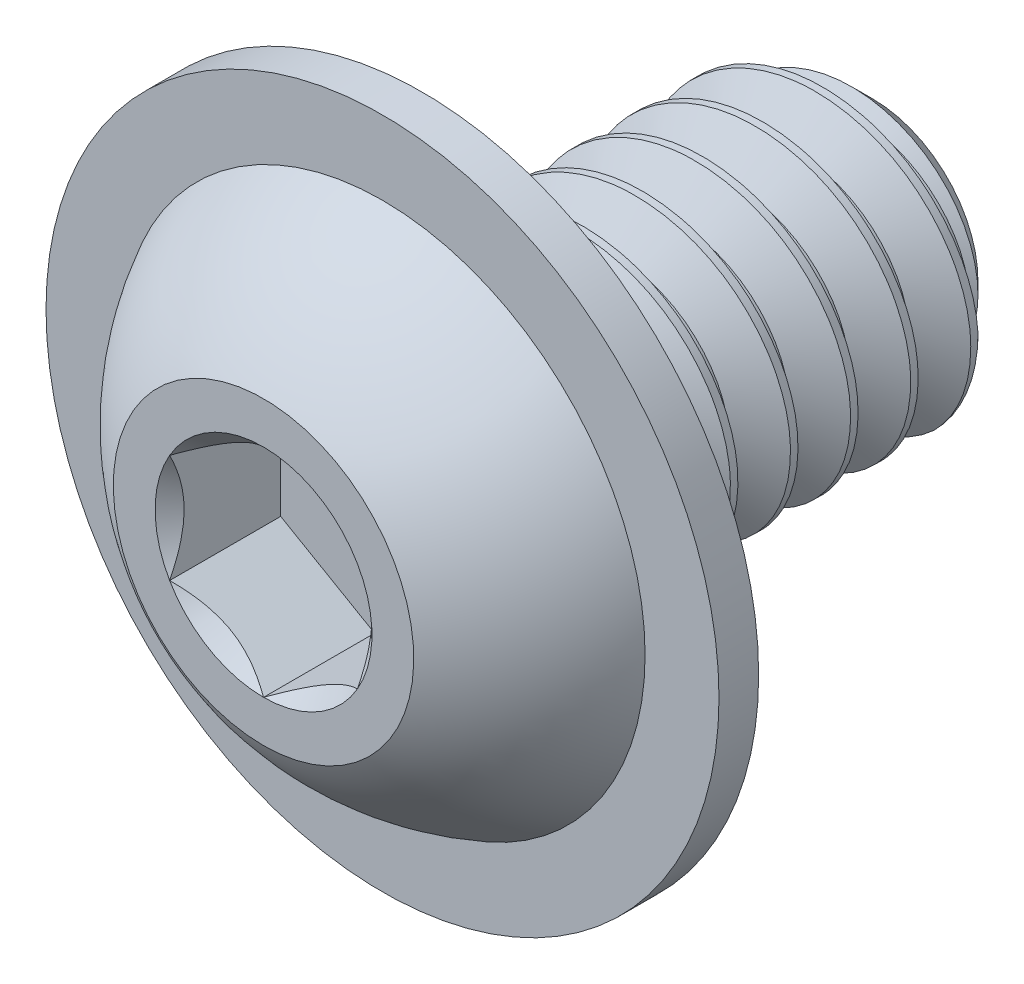
SolidWorks part; units mm, degrees
material "Cast Alloy Steel"
ref_plane "Front" through (0, 0, 0) normal (0, 0, 1) x (1, 0, 0)
ref_plane "Top" through (0, 0, 0) normal (0, 1, 0) x (1, 0, 0)
ref_plane "Right" through (0, 0, 0) normal (1, 0, 0) x (0, 0, -1)
sketch "Sketch1" plane through (0, 0, 0) normal (1, 0, 0) x (0, 0, -1)
  line L2 (3.3528, 3.175) -> (12.8778, 3.175)
  line L3 (12.8778, 3.175) -> (12.8778, 0)
  line L4 (12.8778, 0) -> (3.3528, 0)
  line L6 (2.5146, 5.5499) -> (3.3528, 5.5499) construction
  line L7 (12.8778, 3.175) -> (12.8778, -3.175) construction
  line L8 (0, 0) -> (3.3528, 0) construction
  line L9 (3.3528, 5.5499) -> (3.3528, -5.5499) construction
  line L11 (3.3528, 3.175) -> (3.3528, 0)
  line L13 (0, 1.9844) -> (0, -1.9844) construction
  line L14 (0, 1.9844) -> (0, 3.175) construction
  line L15 (2.5146, 5.5499) -> (2.5146, 7.112) construction
  line L16 (2.5146, 7.112) -> (3.3528, 7.112) construction
  line L17 (3.3528, 7.112) -> (3.3528, 5.5499) construction
  line L18 (3.3528, 7.112) -> (3.3528, -7.112) construction
  arc A3 (0, 3.175) -> (2.5146, 5.5499) centre (5.3774, 0) cw construction
  dimension "D1" = 0.8382
  dimension "Head Ht" = 3.3528
  dimension "Head Dia" = 11.0998
  dimension "Dia" = 6.35
  dimension "Lg" = 9.525
  dimension "Hex" = 3.9688
  dimension "Flange Dia" = 14.224
revolve "Revolve1" add sketch "Sketch1" angle 360 mid plane about L4
sketch "Sketch3" plane through (0, 0, -12.8778) normal (0, 0, -1) x (-1, 0, 0)
  circle A0 centre (0, 0) radius 3.175
curve "Helix/Spiral1" pitch 1.27 height 10.795 radius 3.175 centre (0, 0, -12.8778) axis (0, 0, 1) start towards (0, 1, 0)
sketch "Sketch2" plane through (0, 0, 0) normal (1, 0, 0) x (0, 0, -1)
  line L0 (12.8778, 3.175) -> (13.989, 3.175)
  line L1 (13.989, 3.175) -> (13.5128, 2.3501)
  line L2 (13.5128, 2.3501) -> (13.354, 2.3501)
  line L3 (13.354, 2.3501) -> (12.8778, 3.175)
  line L4 (13.1159, 2.7626) -> (13.7509, 2.7626) construction
  dimension "D1" = 60
  dimension "D2" = 0.1588
  dimension "D3" = 0.635
chamfer "Chamfer1" distance 0.9525 angle 45 1 edges at (0, 3.175, -12.8778)
sweep "Cut-Sweep1" cut profiles "Sketch2" path "Helix/Spiral1"
sketch "Sketch7" plane through (0, 0, 0) normal (1, 0, 0) x (0, 0, -1)
  line L6 (2.5146, 5.5499) -> (3.3528, 5.5499) construction
  line L8 (0, 0) -> (3.3528, 0) construction
  line L11 (3.3528, 5.5499) -> (3.3528, -5.5499) construction
  line L12 (2.5146, 5.5499) -> (3.3528, 5.5499)
  line L13 (0, 0) -> (3.3528, 0)
  line L14 (0, 1.9844) -> (0, -1.9844) construction
  line L15 (3.3528, 5.5499) -> (3.3528, 0)
  line L16 (0, 3.175) -> (0, 0)
  arc A2 (2.5146, 5.5499) -> (0, 3.175) centre (5.3774, 0) ccw construction
  arc A3 (2.5146, 5.5499) -> (0, 3.175) centre (5.3774, 0) ccw
revolve "Revolve2" add sketch "Sketch7" angle 360 mid plane about L13
sketch "Sketch11" plane through (0, 0, -3.3528) normal (0, 0, -1) x (-1, 0, 0)
  circle A0 centre (0, 0) radius 7.112
extrude "Boss-Extrude3" add sketch "Sketch11" against normal up to vertex (0.8382 mm away) up to point (0, 5.5499, -2.5146)
sketch "Sketch5" plane through (0, 0, 0) normal (0, 0, 1) x (1, 0, 0)
  line L1 (1.9844, -1.1457) -> (1.9844, 1.1457)
  line L2 (1.9844, 1.1457) -> (0, 2.2914)
  line L3 (0, 2.2914) -> (-1.9844, 1.1457)
  line L4 (-1.9844, 1.1457) -> (-1.9844, -1.1457)
  line L5 (-1.9844, -1.1457) -> (0, -2.2914)
  line L6 (0, -2.2914) -> (1.9844, -1.1457)
  circle A0 centre (0, 0) radius 1.9844 construction
extrude "Cut-Extrude2" cut sketch "Sketch5" against normal blind 2.347
sketch "Sketch6" plane through (0, 0, 0) normal (0, 0, 1) x (1, 0, 0)
  circle A0 centre (0, 0) radius 2.2914
extrude "Cut-Extrude3" cut sketch "Sketch6" against normal blind 2.347 draft 45
sketch "Sketch9" [suppressed] plane through (0, 0, -5.0546) normal (0, 0, 1) x (1, 0, 0)
  circle A2 centre (0, 0) radius 4.7625
extrude "Boss-Extrude2" [suppressed] add sketch "Sketch9" against normal offset from surface (6.35 mm away) 31.75 up to face at (0, 2.2225, -12.8778)
sketch "Sketch10" plane through (0, 0, 0) normal (1, 0, 0) x (0, 0, -1)
  line L0 (12.8778, 3.175) -> (12.8778, -3.175) construction
  point P0 (10.9728, -3.175)
  dimension "D1" = 1.905
equation "\"D3@Helix/Spiral1\" = \"Lg@Sketch1\" + \"D4@Helix/Spiral1\""
equation "\"D2@Sketch2\" = \"D4@Helix/Spiral1\" * .125"
equation "\"D3@Sketch2\" = \"D4@Helix/Spiral1\" * .5"
equation "\"D1@Chamfer1\" = \"D4@Helix/Spiral1\" * .75"
equation "\"D1@Cut-Extrude2\" = \"Head Ht@Sketch1\" * .7"
equation "\"D1@Sketch1\" = \"Head Ht@Sketch1\" * .25"
equation "\"D1@Sketch10\" = \"D4@Helix/Spiral1\" * 1.5"
equation "\"D1@Cut-Extrude3\" = \"D1@Cut-Extrude2\""
